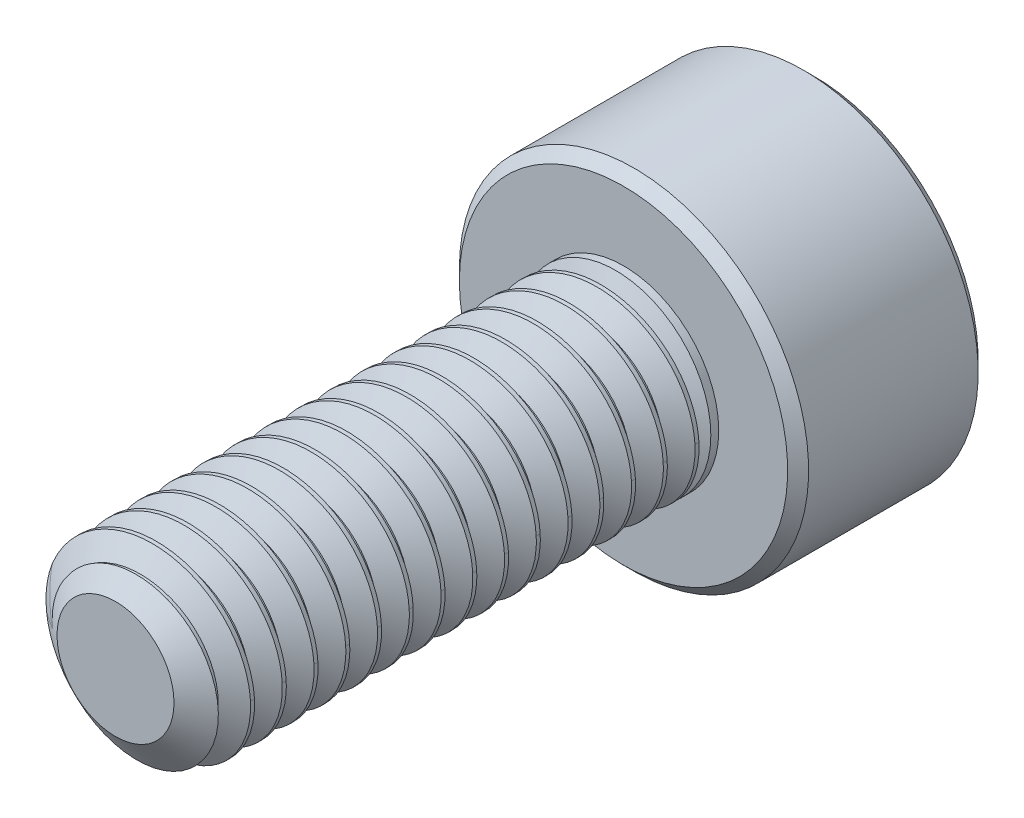
SolidWorks part; units mm, degrees
ref_plane "Front Plane" through (0, 0, 0) normal (0, 0, 1) x (1, 0, 0)
ref_plane "Top Plane" through (0, 0, 0) normal (0, 1, 0) x (1, 0, 0)
ref_plane "Right Plane" through (0, 0, 0) normal (1, 0, 0) x (0, 0, -1)
sketch "Sketch1" plane through (0, 0, 0) normal (0, 0, 1) x (1, 0, 0)
  circle A0 centre (0, 0) radius 1.5
  dimension "OD" = 3
extrude "Extrude1" add sketch "Sketch1" against normal blind 8
sketch "Sketch2" plane through (0, 0, 0) normal (0, 0, 1) x (1, 0, 0)
  circle A0 centre (0, 0) radius 1.5 construction
  circle A1 centre (0, 0) radius 1.5
curve "Helix/Spiral1" pitch 0.5 height 8.5 radius 1.5 centre (0, 0, 0) axis (0, 0, -1) start towards (0, 1, 0) parameters "pitch"=0.5
sketch "Sketch3" plane through (0, 0, 0) normal (1, 0, 0) x (0, 0, -1)
  line L0 (-0.4375, 1.5) -> (-0.25, 1.1752)
  line L1 (-0.25, 1.1752) -> (-0.1875, 1.1752)
  line L2 (-0.1875, 1.1752) -> (0, 1.5)
  line L3 (-0.4375, 1.5) -> (0, 1.5)
  line L4 (-0.2188, 1.5) -> (-0.2188, 1.1752) construction
  line L5 (-0.3438, 1.3376) -> (-0.0938, 1.3376) construction
  line L6 (0, 1.5) -> (0, -1.5) construction
  line L7 (0, -1.5) -> (8, -1.5) construction
  point P11 (2.25, -1.5)
  dimension "D1" = 0.0625
  dimension "D2" = 0.25
  dimension "D3" = 60
  dimension "D4" = 2.25
sweep "Cut-Sweep1" cut profiles "Sketch3" path "Helix/Spiral1"
sketch "Sketch4" plane through (0, 0, 0) normal (1, 0, 0) x (0, 0, -1)
  line L0 (0.4053, 1.5) -> (0, 0.9212)
  line L1 (0, 0.9212) -> (0, 1.5)
  line L2 (0.4053, 1.5) -> (0, 1.5)
  line L3 (-0.4375, 1.5) -> (0, 1.5) construction
  line L4 (0, 0) -> (7.0209, 0) construction
  dimension "D1" = 55
  dimension "D2" = 0.254
revolve "Cut-Revolve1" cut sketch "Sketch4" angle 360 about L4
sketch "Sketch5" plane through (0, 0, 0) normal (1, 0, 0) x (0, 0, -1)
  line L0 (8, -1.1822) -> (8, 1.0703) construction
  line L1 (8, 1.5) -> (0.1202, 1.5)
  line L2 (8, 1.5) -> (8, 0)
  line L3 (8, 0) -> (0, 0)
  line L4 (0, 1.1698) -> (0, 0)
  line L5 (0.1202, 1.5) -> (0, 1.1698)
  line L6 (0, 0) -> (9.9695, 0) construction
  point P3 (0, 1.5)
  point P10 (0, 1.5)
  dimension "D1" = 0.3302
  dimension "D3" = 20
  dimension "Thread Min" = 0
revolve "partially thread" [suppressed] add sketch "Sketch5" angle 360 about L6
sketch "Sketch6" plane through (0, 0, -8) normal (0, 0, -1) x (-1, 0, 0)
  circle A0 centre (0, 0) radius 2.75
  dimension "head dia" = 5.5
extrude "Extrude2" add sketch "Sketch6" along normal blind 3
sketch "Sketch7" plane through (0, 0, -11) normal (0, 0, -1) x (-1, 0, 0)
  line L1 (0, 1.4434) -> (-1.25, 0.7217)
  line L2 (-1.25, 0.7217) -> (-1.25, -0.7217)
  line L3 (-1.25, -0.7217) -> (0, -1.4434)
  line L4 (0, -1.4434) -> (1.25, -0.7217)
  line L5 (1.25, -0.7217) -> (1.25, 0.7217)
  line L6 (1.25, 0.7217) -> (0, 1.4434)
  circle A0 centre (0, 0) radius 1.25 construction
  dimension "hex dia" = 2.5
extrude "Cut-Extrude1" cut sketch "Sketch7" against normal blind 1.875
sketch "Sketch8" plane through (0, 0, -11) normal (0, 0, -1) x (-1, 0, 0)
  circle A0 centre (0, 0) radius 1.4434
extrude "Cut-Extrude2" cut sketch "Sketch8" against normal through all draft 45
chamfer "Chamfer1" distance 0.165 angle 45 2 edges at (-2.75, 0, -11) (-2.75, 0, -8)
sketch "Sketch9" plane through (0, 0, 0) normal (1, 0, 0) x (0, 0, -1)
  line L0 (0, 1.5) -> (0, -1.5) construction
  line L1 (2.75, 1.5) -> (2.75, -1.5) construction
  dimension "D1" = 2.75
sketch "Sketch10" plane through (0, 0, 0) normal (1, 0, 0) x (0, 0, -1)
  line L0 (8, 1.5) -> (8, 0)
  line L1 (8, 1.5) -> (7.875, 1.5)
  line L2 (7.875, 1.5) -> (7.2537, 0)
  line L3 (8, 0) -> (7.2537, 0)
  line L4 (8, 2.585) -> (8, -2.585) construction
  dimension "D1" = 22.5
  dimension "D2" = 0.125
revolve "Revolve1" add sketch "Sketch10" angle 360 about L3
equation "\"D3@Helix/Spiral1\" = \"screw length@Extrude1\"+\"pitch@Helix/Spiral1\""
equation "\"D1@Sketch3\" = \"pitch@Helix/Spiral1\"*.125"
equation "\"D2@Sketch3\" = \"pitch@Helix/Spiral1\"*.5"
equation "\"D1@Cut-Extrude1\" = \"hex dia@Sketch7\"*.75"
equation "\"D1@Chamfer1\" = \"head dia@Sketch6\"*.03"
equation "\"D1@Sketch9\" = \"pitch@Helix/Spiral1\"*5.5"
equation "\"D2@Sketch10\" = \"pitch@Helix/Spiral1\"*.25"
equation "\"D4@Sketch3\" = \"pitch@Helix/Spiral1\"*4.50"
